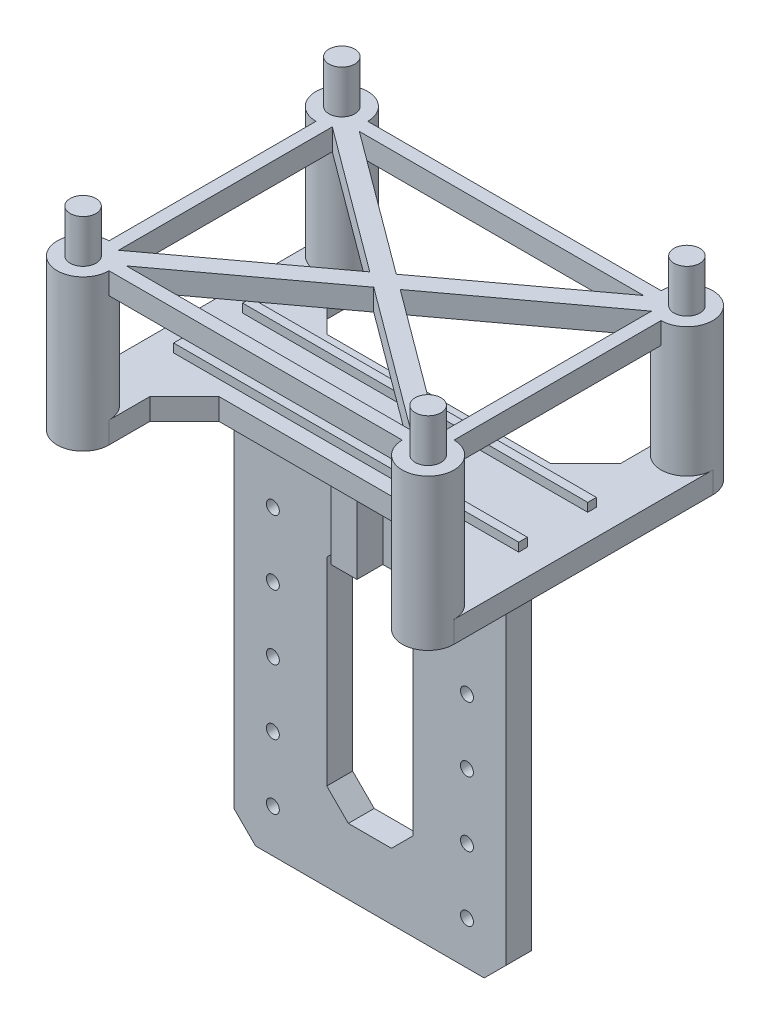
SolidWorks part; units mm, degrees
ref_plane "前视基准面" through (0, 0, 0) normal (0, 0, 1) x (1, 0, 0)
ref_plane "上视基准面" through (0, 0, 0) normal (0, 1, 0) x (1, 0, 0)
ref_plane "右视基准面" through (0, 0, 0) normal (1, 0, 0) x (0, 0, -1)
sketch "草图1" plane through (0, 0, 0) normal (0, 1, 0) x (1, 0, 0)
  line L0 (-30, 0) -> (30, 0)
  line L1 (0, -12.5) -> (0, 12.5)
  line L2 (-43.7056, 12.5) -> (43.7056, 12.5)
  line L3 (-43.7056, -12.5) -> (43.7056, -12.5)
  line L4 (-43.7056, 12.5) -> (-43.7056, -12.5)
  line L5 (43.7056, 12.5) -> (43.7056, -12.5)
  point P4 (0, 0)
  point P7 (0, 0)
  point P10 (0, 12.5)
extrude "凸台-拉伸1" add sketch "草图1" along normal blind 3 contours L2 L4 L3 L1 | L5 L2 L1 L3 region at (-21.8528, 0, 11.9965) region at (0.5035, 0, 6.25)
sketch "草图2" plane through (0, 0, 0) normal (0, -1, 0) x (1, 0, 0)
  line L0 (-30, 0) -> (30, 0)
  circle A0 centre (30, 0) radius 1.5
  circle A1 centre (-30, 0) radius 1.5
  point P4 (0, 0)
extrude "切除-拉伸1" cut sketch "草图2" against normal blind 9 contours A1 | A0 region at (-31.4576, 0, 0)
sketch "草图3" plane through (0, 3, 0) normal (0, 1, 0) x (1, 0, 0)
  line L0 (-40, 0) -> (40, 0)
  line L2 (43.7056, 12.5) -> (43.7056, 25.2811)
  line L4 (0, 0) -> (0, 17.3551)
  line L5 (35.7209, 25.7942) -> (35.7209, 12.5)
  line L6 (-43.7056, 12.5) -> (43.7056, 12.5) construction
  line L7 (43.7056, -12.5) -> (43.7056, -25.2811)
  line L8 (35.7209, -12.5) -> (35.7209, -25.7942)
  line L9 (-43.7056, -12.5) -> (43.7056, -12.5) construction
  line L10 (-43.7056, -12.5) -> (-43.7056, -25.2811)
  line L11 (-35.7209, -12.5) -> (-35.7209, -25.7942)
  line L12 (-35.7209, 25.7942) -> (-35.7209, 12.5)
  line L13 (-43.7056, 12.5) -> (-43.7056, 25.2811)
  line L14 (-43.7056, 12.5) -> (-35.7209, 12.5)
  line L15 (35.7209, 12.5) -> (43.7056, 12.5)
  line L16 (43.7056, -12.5) -> (35.7209, -12.5)
  line L17 (-35.7209, -12.5) -> (-43.7056, -12.5)
  arc A0 (43.7056, 25.2811) -> (35.7209, 25.7942) centre (40, 30) ccw
  arc A1 (43.7056, -25.2811) -> (35.7209, -25.7942) centre (40, -30) cw
  arc A2 (-43.7056, -25.2811) -> (-35.7209, -25.7942) centre (-40, -30) ccw
  arc A3 (-43.7056, 25.2811) -> (-35.7209, 25.7942) centre (-40, 30) cw
  point P4 (0, 0)
  point P7 (40, 0)
  line M7 (-43.7056, -12.5) -> (43.7056, -12.5)
  line M9 (43.7056, 12.5) -> (-43.7056, 12.5)
extrude "凸台-拉伸3" add sketch "草图3" against normal up to surface (3 mm away) contours A3 L13 L12 M9 | L2 A0 L5 M9 | A1 L7 L8 M7 | L10 A2 L11 M7 region at (39.8571, 3, -24.7298) region at (-39.8571, 3, -24.7298) region at (-39.8571, 3, 24.7298) region at (39.8571, 3, 24.7298) up to face at (-30, 0, -1.5)
sketch "草图4" plane through (0, 3, 0) normal (0, 1, 0) x (1, 0, 0)
  line L0 (34, 30) -> (34, -30)
  line L1 (34, -30) -> (46, -30)
  line L2 (46, -30) -> (46, 30)
  line L3 (46, 30) -> (34, 30)
  line L4 (-34, 30) -> (-34, -30)
  line L5 (-34, -30) -> (-46, -30)
  line L6 (-46, -30) -> (-46, 30)
  line L7 (-46, 30) -> (-34, 30)
  arc A0 (43.7056, 25.2811) -> (35.7209, 25.7942) centre (40, 30) ccw construction
  arc A1 (35.7209, -25.7942) -> (43.7056, -25.2811) centre (40, -30) ccw construction
  arc A2 (-35.7209, 25.7942) -> (-43.7056, 25.2811) centre (-40, 30) ccw construction
  arc A3 (-43.7056, -25.2811) -> (-35.7209, -25.7942) centre (-40, -30) ccw construction
extrude "凸台-拉伸4" add sketch "草图4" against normal up to surface (3 mm away) up to face at (-30, 0, -1.5)
sketch "草图5" plane through (0, 3, 0) normal (0, 1, 0) x (1, 0, 0)
  circle A0 centre (40, 30) radius 6
  circle A1 centre (40, -30) radius 6
  circle A2 centre (-40, -30) radius 6
  circle A3 centre (-40, 30) radius 6
extrude "凸台-拉伸5" add sketch "草图5" along normal blind 30
sketch "草图6" plane through (0, 0, 0) normal (0, -1, 0) x (1, 0, 0)
  line L8 (34, 12.5) -> (-34, 12.5)
  line L9 (-34, 12.5) -> (-34, 30)
  line L10 (-46, 30) -> (-46, -30)
  line L11 (-34, -30) -> (-34, -12.5)
  line L12 (-34, -12.5) -> (34, -12.5)
  line L13 (34, -12.5) -> (34, -30)
  line L14 (46, -30) -> (46, 30)
  line L15 (34, 30) -> (34, 12.5)
  line L16 (34, 12.5) -> (-34, 12.5)
  line L17 (-34, 12.5) -> (-34, 30)
  line L18 (-46, 30) -> (-46, -30)
  line L19 (-34, -30) -> (-34, -12.5)
  line L20 (-34, -12.5) -> (34, -12.5)
  line L21 (34, -12.5) -> (34, -30)
  line L22 (46, -30) -> (46, 30)
  line L23 (34, 30) -> (34, 12.5)
  circle A0 centre (-30, 0) radius 1.5 construction
  circle A1 centre (-30, 0) radius 1.5
  circle A2 centre (30, 0) radius 1.5 construction
  circle A3 centre (30, 0) radius 1.5
  arc A4 (-34, 30) -> (-46, 30) centre (-40, 30) ccw
  arc A5 (-46, -30) -> (-34, -30) centre (-40, -30) ccw
  arc A6 (34, -30) -> (46, -30) centre (40, -30) ccw
  arc A7 (46, 30) -> (34, 30) centre (40, 30) ccw
  arc A8 (-34, 30) -> (-46, 30) centre (-40, 30) ccw
  arc A9 (-46, -30) -> (-34, -30) centre (-40, -30) ccw
  arc A10 (34, -30) -> (46, -30) centre (40, -30) ccw
  arc A11 (46, 30) -> (34, 30) centre (40, 30) ccw
  dimension "D1" = 0
sketch "草图7" plane through (0, 3, 0) normal (0, 1, 0) x (1, 0, 0)
  line L0 (0, -7) -> (0, 7)
  line L1 (-40, 7) -> (40, 7)
  line L2 (-40, 7) -> (-40, 9)
  line L3 (-40, 9) -> (40, 9)
  line L4 (40, 9) -> (40, 7)
  line L5 (0, 0) -> (14.7785, 0)
  line L6 (-40, -9) -> (40, -9)
  line L7 (-40, -7) -> (-40, -9)
  line L8 (-40, -7) -> (40, -7)
  line L9 (40, -9) -> (40, -7)
  point P4 (0, 0)
  point P8 (0, 7)
extrude "凸台-拉伸7" add sketch "草图7" along normal blind 2 contours L6 L9 L8 L7 | L1 L4 L3 L2 region at (0, 3, 8)
sketch "草图8" plane through (0, 33, 0) normal (0, 1, 0) x (1, 0, 0)
  circle A0 centre (-40, -30) radius 3
  circle A1 centre (-40, 30) radius 3
  circle A2 centre (40, 30) radius 3
  circle A3 centre (40, -30) radius 3
extrude "凸台-拉伸8" add sketch "草图8" along normal blind 10
chamfer "倒角1" distance 8 angle 45 4 edges at (-34, 1.5, 12.5) (-34, 1.5, -12.5) (34, 1.5, -12.5) (34, 1.5, 12.5)
sketch "草图9" plane through (0, 33, 0) normal (0, 1, 0) x (1, 0, 0)
  line L0 (40, -30) -> (40, 30)
  line L1 (40, 30) -> (-40, 30)
  line L2 (-40, 30) -> (-40, -30)
  line L3 (-40, -30) -> (40, -30)
  line L4 (32.9474, 27) -> (-32.9474, 27)
  line L5 (0, 2.6104) -> (32.9474, 27)
  line L6 (-37, 24.7792) -> (-37, -24.7792)
  line L8 (-32.9474, -27) -> (32.9474, -27)
  line L9 (0, 2.6104) -> (-32.9474, 27)
  line L10 (37, -24.7792) -> (37, 24.7792)
  line L13 (-37, 24.7792) -> (-3.5263, 0)
  line L14 (37, -24.7792) -> (3.5263, 0)
  line L15 (-37, -24.7792) -> (-3.5263, 0)
  line L16 (37, 24.7792) -> (3.5263, 0)
  line L17 (0, -2.6104) -> (32.9474, -27)
  line L18 (0, -2.6104) -> (-32.9474, -27)
extrude "凸台-拉伸9" add sketch "草图9" against normal blind 5
sketch "草图10" plane through (0, 0, 0) normal (0, -1, 0) x (1, 0, 0)
  line L12 (26, 12.5) -> (-26, 12.5)
  line L13 (-26, 12.5) -> (-34, 20.5)
  line L14 (-34, 20.5) -> (-34, 30)
  line L15 (-46, 30) -> (-46, -30)
  line L16 (-34, -30) -> (-34, -20.5)
  line L17 (-34, -20.5) -> (-26, -12.5)
  line L18 (-26, -12.5) -> (26, -12.5)
  line L19 (26, -12.5) -> (34, -20.5)
  line L20 (34, -20.5) -> (34, -30)
  line L21 (46, -30) -> (46, 30)
  line L22 (34, 30) -> (34, 20.5)
  line L23 (34, 20.5) -> (26, 12.5)
  line L24 (26, 12.5) -> (-26, 12.5)
  line L25 (-26, 12.5) -> (-34, 20.5)
  line L26 (-34, 20.5) -> (-34, 30)
  line L27 (-46, 30) -> (-46, -30)
  line L28 (-34, -30) -> (-34, -20.5)
  line L29 (-34, -20.5) -> (-26, -12.5)
  line L30 (-26, -12.5) -> (26, -12.5)
  line L31 (26, -12.5) -> (34, -20.5)
  line L32 (34, -20.5) -> (34, -30)
  line L33 (46, -30) -> (46, 30)
  line L34 (34, 30) -> (34, 20.5)
  line L35 (34, 20.5) -> (26, 12.5)
  circle A0 centre (-30, 0) radius 1.5 construction
  circle A1 centre (-30, 0) radius 1.5
  circle A2 centre (30, 0) radius 1.5 construction
  circle A3 centre (30, 0) radius 1.5
  arc A4 (-34, 30) -> (-46, 30) centre (-40, 30) ccw
  arc A5 (-46, -30) -> (-34, -30) centre (-40, -30) ccw
  arc A6 (34, -30) -> (46, -30) centre (40, -30) ccw
  arc A7 (46, 30) -> (34, 30) centre (40, 30) ccw
  arc A8 (-34, 30) -> (-46, 30) centre (-40, 30) ccw
  arc A9 (-46, -30) -> (-34, -30) centre (-40, -30) ccw
  arc A10 (34, -30) -> (46, -30) centre (40, -30) ccw
  arc A11 (46, 30) -> (34, 30) centre (40, 30) ccw
  dimension "D1" = 0
extrude "凸台-拉伸11" add sketch "草图10" along normal blind 2
sketch "草图12" plane through (0, -2, 0) normal (0, -1, 0) x (1, 0, 0)
  line L1 (31.5, 0) -> (31.5, 3.5)
  line L2 (31.5, 3.5) -> (-31.5, 3.5)
  line L3 (-31.5, 3.5) -> (-31.5, -3.5)
  line L5 (31.5, -3.5) -> (31.5, 0)
  line L6 (31.5, 0) -> (31.5, -3.5)
  line L7 (31.5, -3.5) -> (-31.5, -3.5)
  line L8 (-31.5, -3.5) -> (-31.5, 3.5)
  circle A0 centre (30, 0) radius 1.5 construction
  circle M1 centre (-30, 0) radius 1.5
  circle M18 centre (30, 0) radius 1.5
extrude "凸台-拉伸13" add sketch "草图12" along normal blind 90 and the other way up to surface contours L7 L5 L1 L2 L3 M18 M1 | M1 | M18 region at (-30, -2, 0) region at (0, -2, 0) region at (30, -2, 0) other way up to face at (0, 3, -8)
sketch "草图14" plane through (0, 0, -3.5) normal (0, 0, -1) x (-1, 0, 0)
  line L0 (0, 33) -> (0, -82)
  line L1 (-34, 33) -> (34, 33) construction
  line L2 (22.5, -82) -> (-22.5, -82)
  circle A0 centre (-22.5, -82) radius 1.5
  circle A1 centre (22.5, -82) radius 1.5
  circle A2 centre (22.5, -67) radius 1.5
  circle A3 centre (-22.5, -67) radius 1.5
  circle A4 centre (22.5, -52) radius 1.5
  circle A5 centre (-22.5, -52) radius 1.5
  circle A6 centre (22.5, -37) radius 1.5
  circle A7 centre (-22.5, -37) radius 1.5
  circle A8 centre (22.5, -22) radius 1.5
  circle A9 centre (-22.5, -22) radius 1.5
  point P8 (0, -82)
  dimension "D1" = 5
extrude "切除-拉伸2" cut sketch "草图14" against normal blind 90 contours A6 | A4 | A5 | A3 | A2 | A0 | A1 | A8 | A9 | A7 region at (23.9576, -82, -3.5) region at (-22.5, -80.5424, -3.5) region at (-22.5, -67, -3.5) region at (22.5, -67, -3.5) region at (-22.5, -52, -3.5) region at (22.5, -52, -3.5) region at (-22.5, -37, -3.5)
sketch "草图15" plane through (0, 0, 3.5) normal (0, 0, 1) x (1, 0, 0)
  line L0 (0, -2) -> (0, -92)
  line L1 (31.5, -2) -> (-31.5, -2) construction
  line L2 (31.5, -92) -> (-31.5, -92) construction
sketch "草图17" plane through (0, 0, 3.5) normal (0, 0, 1) x (1, 0, 0)
  line L0 (0, -2) -> (40, -2)
  line L1 (34, -2) -> (46, -2) construction
  line L2 (40, -2) -> (40, -92)
  line L3 (40, -92) -> (31.5, -92)
  line L4 (31.5, -92) -> (31.5, -2)
  line L5 (31.5, -2) -> (40, -2)
  line L6 (0, -2) -> (0, -92)
  line L7 (-31.5, -2) -> (-40, -2)
  line L8 (-31.5, -92) -> (-31.5, -2)
  line L9 (-40, -92) -> (-31.5, -92)
  line L10 (-40, -2) -> (-40, -92)
sketch "草图20" plane through (0, 0, -3.5) normal (0, 0, -1) x (-1, 0, 0)
  line L0 (0, -20.7381) -> (0, -76.708)
  line L1 (0, -2) -> (0, -92) construction
  line L2 (-10, -76.708) -> (10, -76.708)
  line L3 (10, -76.708) -> (10, -20.7381)
  line L4 (10, -20.7381) -> (-10, -20.7381)
  line L5 (-10, -20.7381) -> (-10, -76.708)
  point P7 (0, -76.708)
extrude "切除-拉伸3" cut sketch "草图20" against normal through all contours L4 L5 L2 L0 | L3 L4 L0 L2 region at (-5, -48.7231, -3.5) region at (5, -48.7231, -3.5)
chamfer "倒角2" distance 5 angle 45 4 edges at (10, -76.708, 0) (-10, -76.708, 0) (10, -20.7381, 0) (-10, -20.7381, 0)
sketch "草图21" plane through (0, 0, 3.5) normal (0, 0, 1) x (1, 0, 0)
  line L0 (0, -2) -> (3, -2)
  line L1 (31.5, -2) -> (-31.5, -2) construction
  line L2 (3, -2) -> (3, -20.7381)
  line L3 (5, -20.7381) -> (-5, -20.7381) construction
  line L4 (3, -20.7381) -> (-3, -20.7381)
  line L5 (-3, -20.7381) -> (-3, -2)
  line L6 (26, -2) -> (-26, -2) construction
  line L7 (-3, -2) -> (3, -2)
  line M1 (-5, -20.7381) -> (5, -20.7381)
  line M20 (31.5, -2) -> (-31.5, -2)
extrude "凸台-拉伸16" add sketch "草图21" along normal blind 6 contours L5 L2 M1 M20 region at (0, -11.369, 3.5)
sketch "草图22" plane through (0, 0, -3.5) normal (0, 0, -1) x (-1, 0, 0)
  line L0 (0, 33) -> (0, -82)
  line L1 (0, -2) -> (0, -92) construction
sketch "草图23" plane through (0, 0, -3.5) normal (0, 0, -1) x (-1, 0, 0)
  line L4 (31.5, -2) -> (-31.5, -2)
  line L5 (-31.5, -2) -> (-31.5, -92)
  line L6 (-31.5, -92) -> (31.5, -92)
  line L7 (31.5, -92) -> (31.5, -2)
  line L8 (31.5, -2) -> (-31.5, -2)
  line L9 (-31.5, -2) -> (-31.5, -92)
  line L10 (-31.5, -92) -> (31.5, -92)
  line L11 (31.5, -92) -> (31.5, -2)
  dimension "D1" = 0
extrude "切除-拉伸4" cut sketch "草图23" against normal blind 1
chamfer "倒角3" distance 5 angle 45 5 edges at (-17.25, -2, 3.5) (-31.5, -2, 0.5) (17.25, -2, 3.5) (0, -2, -2.5) (31.5, -2, 0.5)
chamfer "倒角4" distance 5 angle 45 2 edges at (-31.5, -92, 0.5) (31.5, -92, 0.5)
